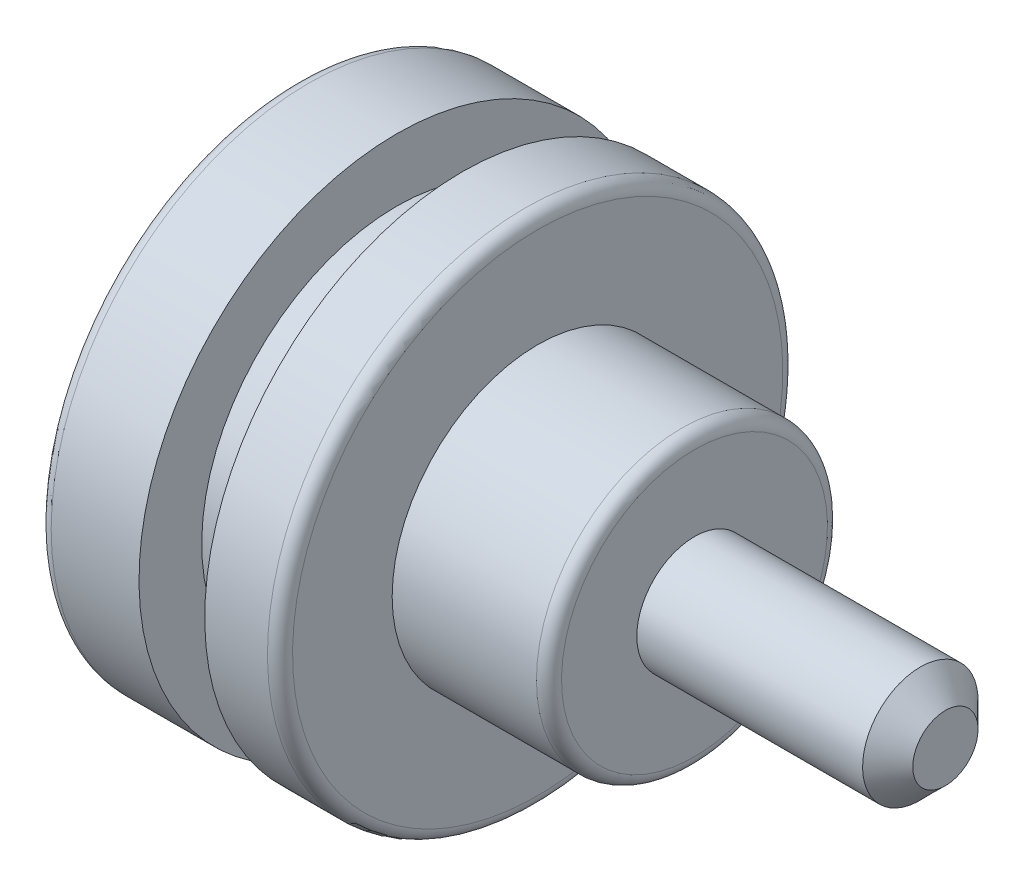
SolidWorks part; units mm, degrees
material "Cobre"
ref_plane "Plano frontal" through (0, 0, 0) normal (0, 0, 1) x (1, 0, 0)
ref_plane "Plano superior" through (0, 0, 0) normal (0, 1, 0) x (1, 0, 0)
ref_plane "Plano direito" through (0, 0, 0) normal (1, 0, 0) x (0, 0, -1)
sketch "Esboço1" plane through (0, 0, 0) normal (0, 0, 1) x (1, 0, 0)
  line L0 (0, 5) -> (0, 10.27)
  line L1 (0, 10.27) -> (4, 10.27)
  line L2 (4, 10.27) -> (4, 7.77)
  line L3 (4, 7.77) -> (6.62, 7.77)
  line L4 (6.62, 7.77) -> (6.62, 10.27)
  line L5 (6.62, 10.27) -> (9.62, 10.27)
  line L6 (9.62, 10.27) -> (9.62, 5.8)
  line L7 (9.62, 5.8) -> (15.87, 5.8)
  line L8 (25.87, 1.3) -> (25.87, 0)
  line L9 (25.87, 0) -> (9.3868, 0)
  line L10 (6.5, 5) -> (9.3868, 0)
  line L11 (6.5, 5) -> (0, 5)
  line L12 (14.62, -982.7136) -> (14.62, 49017.2864) construction
  line L13 (2.62, -1013.2056) -> (2.62, 48986.7944) construction
  line L14 (15.87, 5.8) -> (15.87, 2.3)
  line L15 (15.87, 2.3) -> (24.87, 2.3)
  line L16 (24.87, 2.3) -> (25.87, 1.3)
  point P10 (25.87, 2.3)
  dimension "D1" = 1
  dimension "D2" = 7.77
  dimension "D3" = 2.62
  dimension "D4" = 2.5
  dimension "D5" = 2.5
  dimension "D6" = 6.5
  dimension "D7" = 4
  dimension "D8" = 3
  dimension "D9" = 5.8
  dimension "D10" = 2.3
  dimension "D11" = 60
  dimension "D12" = 12
  dimension "D13" = 5
  dimension "D14" = 10.27
  dimension "D15" = 5
  dimension "D16" = 6.25
  dimension "D17" = 10
revolve "Revolução1" add sketch "Esboço1" angle 360 about L9
cosmetic thread "Representação de rosca2" parameters "D2"=11.1125
cosmetic thread "Representação de rosca3" parameters "D2"=9.6012
fillet "Filete2" radius 0.5 1 edges at (0, 5, 0)
fillet "Filete3" radius 0.5 1 edges at (0, 10.27, 0)
fillet "Filete4" radius 0.5 1 edges at (9.62, 10.27, 0)
fillet "Filete5" radius 0.5 1 edges at (15.87, 5.8, 0)
ref_plane "Plano1" through (0, 0, -10.27) normal (0, 0, -1) x (-1, 0, 0)
ref_axis "Eixo1" through (27.1635, 0, -10.27) along (-1, 0, 0)
sketch "Esboço5" plane through (0, 0, -10.27) normal (0, 0, -1) x (-1, 0, 0)
  line L0 (-27.1635, 0) -> (1.2935, 0) construction
  line L1 (-0.5, -10.27) -> (-0.5, 10.27) construction
  circle A0 centre (-2, 0) radius 1
  dimension "D1" = 2
  dimension "D2" = 1.5
extrude "Corte-extrusão1" cut sketch "Esboço5" against normal blind 3
chamfer "Chanfro1" distance 1 angle 45 1 edges at (1, 0, -7.27)
